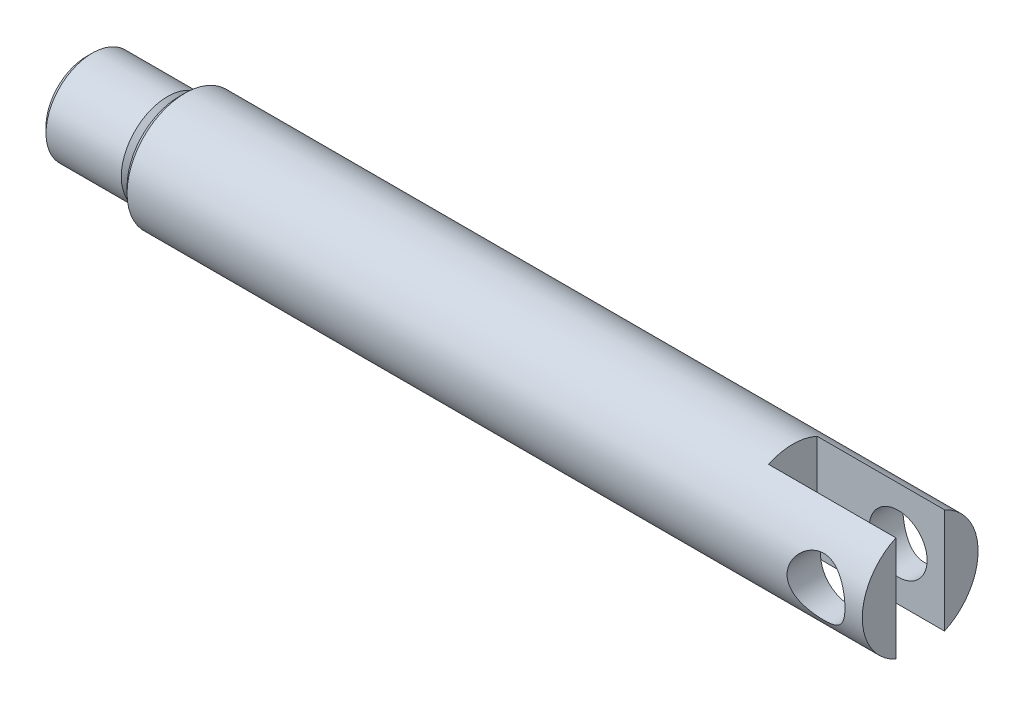
SolidWorks part; units mm, degrees
ref_plane "Front Plane" through (0, 0, 0) normal (0, 0, 1) x (1, 0, 0)
ref_plane "Top Plane" through (0, 0, 0) normal (0, 1, 0) x (1, 0, 0)
ref_plane "Right Plane" through (0, 0, 0) normal (1, 0, 0) x (0, 0, -1)
sketch "Sketch1" plane through (0, 0, 0) normal (0, 0, 1) x (1, 0, 0)
  line L0 (0, 0) -> (36, 0)
  line L1 (0, 0) -> (0, -2)
  line L2 (0, -2) -> (3.5, -2)
  line L3 (3.5, -2) -> (3.5, -1.75)
  line L4 (3.5, -1.75) -> (4, -1.75)
  line L5 (4, -1.75) -> (4, -2.5)
  line L6 (4, -2.5) -> (36, -2.5)
  line L7 (36, -2.5) -> (36, 0)
  dimension "D1" = 36
  dimension "D2" = 2
  dimension "D3" = 2.5
  dimension "D4" = 3.5
  dimension "D5" = 1.75
  dimension "D6" = 4
revolve "Revolve1" add sketch "Sketch1" angle 360 about L0
sketch "Sketch2" plane through (0, 0, 0) normal (0, 0, 1) x (1, 0, 0)
  line L0 (36, -2.5) -> (36, 2.5) construction
  circle A0 centre (34, 0) radius 1.25
  point P4 (0, 0)
  dimension "D2" = 2.5
  dimension "D1" = 2
extrude "Cut-Extrude1" cut sketch "Sketch2" against normal mid plane 10
sketch "Sketch3" plane through (36, 0, 0) normal (1, 0, 0) x (0, 0, -1)
  line L1 (-1.05, -4.138) -> (1.05, -4.138)
  line L2 (-1.05, -4.138) -> (-1.05, 4.138)
  line L3 (-1.05, 4.138) -> (1.05, 4.138)
  line L4 (1.05, -4.138) -> (1.05, 4.138)
  line L5 (-1.05, -4.138) -> (1.05, 4.138) construction
  line L6 (-1.05, 4.138) -> (1.05, -4.138) construction
  point P0 (0, 0)
  dimension "D1" = 2.1
  dimension "D2" = 8.276
extrude "Cut-Extrude2" cut sketch "Sketch3" against normal blind 5.5
chamfer "Chamfer1" distance 0.25 angle 45 3 edges at (0, 0, 2) (4, 0, 2.5) (3.5, 0, 1.75)
